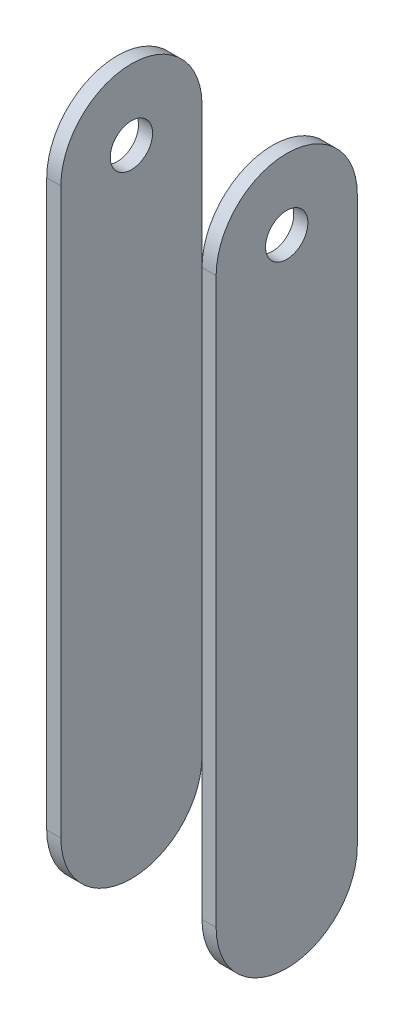
SolidWorks part; units mm, degrees
material "Commercially Pure CP-Ti UNS R50700  Grade 4 (SS)"
ref_plane "Front Plane" through (0, 0, 0) normal (0, 0, 1) x (1, 0, 0)
ref_plane "Top Plane" through (0, 0, 0) normal (0, 1, 0) x (1, 0, 0)
ref_plane "Right Plane" through (0, 0, 0) normal (1, 0, 0) x (0, 0, -1)
sketch "Sketch1" plane through (0, 0, 0) normal (1, 0, 0) x (0, 0, -1)
  line L0 (0, 0) -> (0, 127) construction
  line L1 (-15.875, 0) -> (-15.875, 127)
  line L2 (15.875, 0) -> (15.875, 127)
  arc A0 (-15.875, 0) -> (15.875, 0) centre (0, 0) ccw
  arc A1 (15.875, 127) -> (-15.875, 127) centre (0, 127) ccw
  circle A2 centre (0, 127) radius 4.7625
  point P3 (0, 63.5)
  dimension "D3" = 9.525
  dimension "D1" = 127
  dimension "D2" = 31.75
extrude "Boss-Extrude1" add sketch "Sketch1" against normal blind 3.175 from offset 19.05
mirror "Mirror3" about plane through (0, 0, 0) normal (1, 0, 0) of bodies 101
